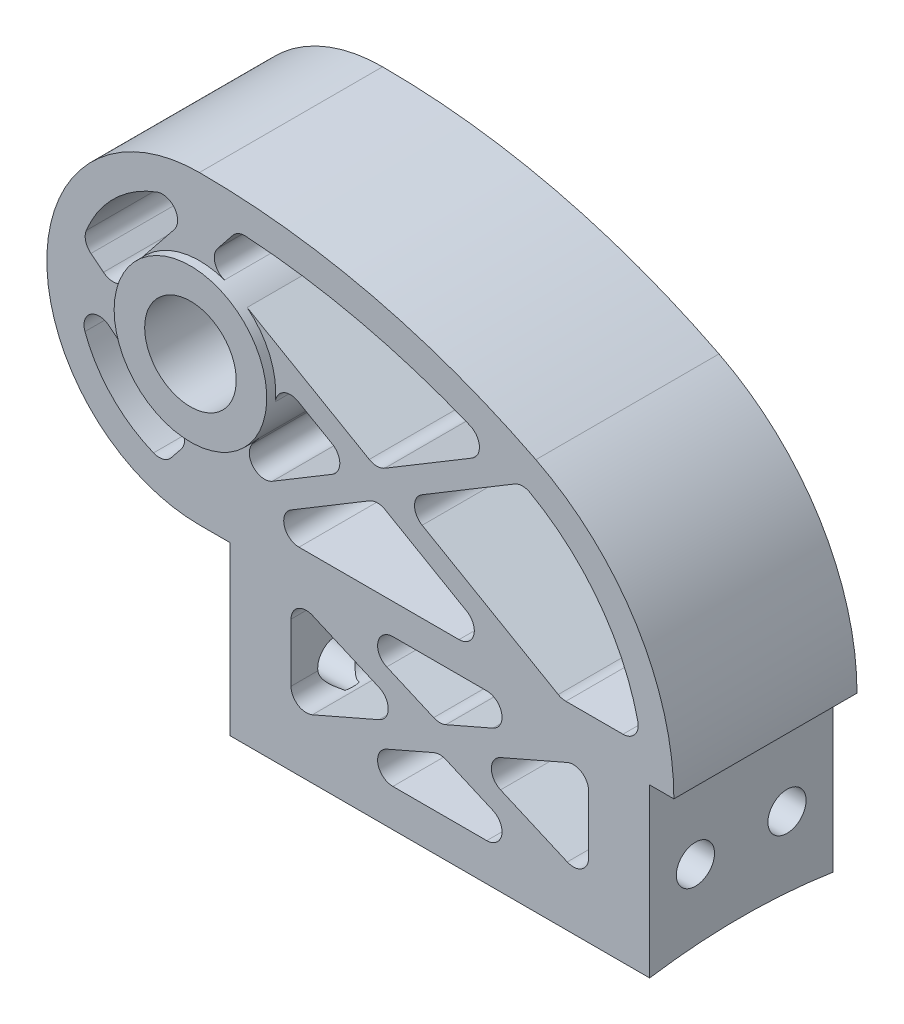
SolidWorks part; units mm, degrees
note: '?' marks a value the reader was unsure of.
material "7075-T6 (SN)"
ref_plane "Front Plane" through (0, 0, 0) normal (0, 0, 1) x (1, 0, 0)
ref_plane "Top Plane" through (0, 0, 0) normal (0, 1, 0) x (1, 0, 0)
ref_plane "Right Plane" through (0, 0, 0) normal (1, 0, 0) x (0, 0, -1)
sketch "frontal_shape" plane through (0, 0, 0) normal (0, 0, 1) x (1, 0, 0)
  line L0 (2, -10) -> (0, -10)
  line L1 (2, -10) -> (29.5, -10) construction
  line L2 (2, -10) -> (2, -20.5)
  line L3 (2, -20.5) -> (29.5, -20.5)
  line L4 (29.5, -10) -> (29.5, -20.5)
  line L5 (29.5, -10) -> (31.0875, -10)
  line L6 (31.0875, -10) -> (31.0875, -20.5) construction
  line L7 (31.0875, -20.5) -> (29.5, -20.5) construction
  line L8 (22.0449, 4.7276) -> (0, -8) construction
  line L9 (0, -10) -> (0, -8) construction
  circle A0 centre (0, 0) radius 3
  arc A1 (0, 10) -> (0, -10) centre (0, 0) ccw
  arc A2 (0, 10) -> (22.0449, 4.7276) centre (0, -38.7233) cw
  arc A3 (31.0875, -10) -> (22.0449, 4.7276) centre (14.5728, -10) ccw
  circle A4 centre (0, 0) radius 5
  point P7 (15.75, -10)
  point P16 (15.75, -20.5)
  dimension "shoulder_bold_diam" = 6
  dimension "abad_outer_diam" = 20
  dimension "spacer_diam" = 10
  dimension "plate_thickness" = 1.5875
  dimension "motor_thickness" = 27.5
  dimension "tab_height" = 10.5
  dimension "rotation_axis_to_motor_face" = 2
  dimension "wall_thickness" = 2
  dimension "support_angle" = 30
ref_plane "Plane1" through (2, 0, 0) normal (1, 0, 0) x (0, 0, -1)
sketch "sagittal_shape" plane through (2, 0, 0) normal (1, 0, 0) x (0, 0, -1)
  line L0 (0, -60) -> (0, -20.5) construction
  line L1 (0, -10) -> (0, -20.5) construction
  line L2 (0, 10) -> (0, 4.7276) construction
  line L4 (-6, -20.9584) -> (-6, 10)
  line L5 (-6, 10) -> (6, 10)
  line L6 (6, -20.9584) -> (6, 10)
  line L7 (6, 0) -> (6.59, 0) construction
  circle A0 centre (0, -60) radius 39.5 construction
  arc A1 (-6, -20.9584) -> (6, -20.9584) centre (0, -60) cw
  point P12 (0, 10)
  dimension "motor_diam" = 79
  dimension "thickness" = 12
  dimension "spacer_thickness" = 0.59
sketch "inner_structure" plane through (0, 0, 0) normal (0, 0, 1) x (1, 0, 0)
  line L2 (2, -10) -> (29.5, -10) construction
  line L5 (-3.9031, 3.125) -> (3.125, 3.9031) construction
  line L6 (3.125, 3.9031) -> (3.9031, -3.125) construction
  line L7 (-3.125, -3.9031) -> (-3.9031, 3.125) construction
  line L8 (3.9031, -3.125) -> (-3.125, -3.9031) construction
  line L10 (0, -8) -> (28.949, -8) construction
  line L11 (2, -18.5) -> (6, -18.5) construction
  line L12 (6, -10) -> (25.5, -10) construction
  line L13 (6, -10) -> (6, -18.5) construction
  line L14 (6, -18.5) -> (25.5, -18.5) construction
  line L15 (25.5, -10) -> (25.5, -18.5) construction
  line L16 (2, -10) -> (2, -20.5) construction
  line L17 (25.5, -18.5) -> (29.5, -18.5) construction
  line L18 (29.5, -10) -> (29.5, -20.5) construction
  line L19 (0, 8) -> (0, 10) construction
  line L20 (6, -18.5) -> (6, -20.5) construction
  line L21 (2, -20.5) -> (29.5, -20.5) construction
  line L22 (6, -10) -> (25.5, -18.5) construction
  line L23 (25.5, -10) -> (6, -18.5) construction
  line L24 (0, 8) -> (-3.9031, 3.125) construction
  line L25 (2.5081, 7.9326) -> (0.1581, 4.9975) construction
  line L26 (-8, 0) -> (-3.125, -3.9031) construction
  line L27 (-7.6643, 2.2932) -> (-4.9975, 0.1581) construction
  line L28 (-2.2932, -7.6643) -> (-0.1581, -4.9975) construction
  line L29 (3.9031, -3.125) -> (0, -8) construction
  line L30 (3.125, 3.9031) -> (23.7418, -8) construction
  line L31 (20.7418, -8) -> (4.8615, 1.1685) construction
  line L32 (0, -8) -> (19.4415, 3.6738) construction
  line L33 (2.9138, -8) -> (21.14, 2.944) construction
  line L34 (1.3331, 6.4651) -> (-0.2281, 7.7151) construction
  line L35 (-6.3309, 1.2257) -> (-7.5809, -0.3356) construction
  line L36 (-1.2257, -6.3309) -> (0.3356, -7.5809) construction
  line L37 (12.8017, -3.4158) -> (13.5517, -2.1167) construction
  line L38 (9.7207, -2.1631) -> (10.4929, -3.4491) construction
  line L39 (7.8769, -10) -> (15.75, -13.4318) construction
  line L40 (15.75, -13.4318) -> (23.6231, -10) construction
  line L41 (25.5, -10.8182) -> (17.6269, -14.25) construction
  line L42 (17.6269, -14.25) -> (25.5, -17.6818) construction
  line L43 (7.8769, -18.5) -> (15.75, -15.0682) construction
  line L44 (15.75, -15.0682) -> (23.6231, -18.5) construction
  line L46 (6, -10.8182) -> (13.8731, -14.25) construction
  line L47 (13.8731, -14.25) -> (6, -17.6818) construction
  line L48 (11.8135, -11.7159) -> (11.2141, -13.091) construction
  line L49 (9.9365, -15.9659) -> (10.5359, -17.341) construction
  arc A1 (0, 8) -> (0, -8) centre (0, 0) ccw construction
  circle A2 centre (0, 0) radius 5 construction
  arc A4 (29.0875, -10) -> (21.14, 2.944) centre (14.5728, -10) ccw
  arc A5 (21.14, 2.944) -> (0, 8) centre (0, -38.7233) ccw
  arc A6 (28.949, -8) -> (21.14, 2.944) centre (14.5728, -10) ccw construction
  arc A7 (21.14, 2.944) -> (0, 8) centre (0, -38.7233) ccw construction
  point P71 (10.2362, -16.6534)
  point P74 (11.5138, -12.4034)
  dimension "thread_thickness" = 4
  dimension "internal_thickness" = 1.5
  dimension "hub_thickness" = 2
  dimension "wall_thickness" = 2
  dimension "support_angle" = 30
sketch "Sketch4" plane through (0, 0, 0) normal (0, 0, 1) x (1, 0, 0)
  line L0 (2, -10) -> (2, -20.5) construction
  line L2 (29.5, -10) -> (29.5, -20.5) construction
  line L3 (29.5, -10) -> (31.0875, -10) construction
  line L4 (2, -10) -> (0, -10) construction
  line L5 (2, -10) -> (2, -20.9584)
  line L6 (2, -20.9584) -> (29.5, -20.9584)
  line L7 (29.5, -10) -> (29.5, -20.9584)
  line L8 (29.5, -10) -> (31.0875, -10)
  line L9 (2, -10) -> (0, -10)
  arc A0 (0, 10) -> (0, -10) centre (0, 0) ccw construction
  arc A1 (22.0449, 4.7276) -> (0, 10) centre (0, -38.7233) ccw construction
  arc A2 (0, 10) -> (0, -10) centre (0, 0) ccw
  arc A3 (22.0449, 4.7276) -> (0, 10) centre (0, -38.7233) ccw
  arc A4 (31.0875, -10) -> (22.0449, 4.7276) centre (14.5728, -10) ccw construction
  arc A5 (31.0875, -10) -> (22.0449, 4.7276) centre (14.5728, -10) ccw
  circle A6 centre (0, 0) radius 3 construction
  circle A7 centre (0, 0) radius 3
extrude "primary_shape" add sketch "Sketch4" against normal up to vertex (6 mm away) and the other way up to vertex (6 mm away) up to point (2, 10, -6) other way up to point (2, 10, 6)
sketch "Sketch5" plane through (0, 0, -6) normal (0, 0, -1) x (-1, 0, 0)
  circle A0 centre (0, 0) radius 3
  circle A1 centre (0, 0) radius 5
  circle A2 centre (0, 0) radius 3 construction
  circle A3 centre (0, 0) radius 5 construction
extrude "spacer" add sketch "Sketch5" along normal up to vertex (0.59 mm away) up to point (2, 0, -6.59)
mirror "spacer_mirror" about plane through (0, 0, 0) normal (0, 0, 1) of "spacer"
sketch "Sketch7" plane through (2, 0, 0) normal (-1, 0, 0) x (0, 0, 1)
  line L0 (-6, -20.9584) -> (6, -20.9584) construction
  line L1 (-6, -20.9584) -> (6, -20.9584)
  arc A0 (-6, -20.9584) -> (6, -20.9584) centre (0, -60) cw
extrude "motor_cuttout" cut sketch "Sketch7" against normal up to next
sketch "Sketch8" plane through (0, 0, 6) normal (0, 0, 1) x (1, 0, 0)
  line L0 (7.8769, -10) -> (15.75, -13.4318)
  line L1 (15.75, -13.4318) -> (23.6231, -10)
  line L2 (23.6231, -10) -> (7.8769, -10)
  line L3 (6, -10.8182) -> (13.8731, -14.25)
  line L4 (13.8731, -14.25) -> (6, -17.6818)
  line L5 (6, -17.6818) -> (6, -10.8182)
  line L6 (7.8769, -18.5) -> (15.75, -15.0682)
  line L7 (15.75, -15.0682) -> (23.6231, -18.5)
  line L8 (23.6231, -18.5) -> (7.8769, -18.5)
  line L9 (25.5, -10.8182) -> (25.5, -17.6818)
  line L10 (25.5, -17.6818) -> (17.6269, -14.25)
  line L11 (17.6269, -14.25) -> (25.5, -10.8182)
  line L12 (2.9138, -8) -> (11.6529, -2.7525)
  line L13 (20.7418, -8) -> (4.8615, 1.1685) construction
  line L14 (2.9138, -8) -> (21.14, 2.944) construction
  line L15 (11.6529, -2.7525) -> (20.7418, -8)
  line L16 (20.7418, -8) -> (2.9138, -8)
  line L17 (21.14, 2.944) -> (13.1235, -1.8695)
  line L18 (3.125, 3.9031) -> (23.7418, -8) construction
  line L19 (13.1235, -1.8695) -> (23.7418, -8)
  line L20 (23.7418, -8) -> (28.949, -8)
  line L21 (19.5258, 3.7244) -> (11.638, -1.0119)
  line L22 (0, -8) -> (19.4415, 3.6738) construction
  line L23 (11.638, -1.0119) -> (3.125, 3.9031)
  line L24 (0.1581, 4.9975) -> (2.5081, 7.9326)
  line L25 (4.8615, 1.1685) -> (10.1674, -1.8949)
  line L26 (10.1674, -1.8949) -> (0, -8)
  line L27 (0, -8) -> (3.9031, -3.125)
  line L28 (-0.1581, -4.9975) -> (-2.2932, -7.6643)
  line L29 (-8, 0) -> (-3.125, -3.9031)
  line L30 (-7.6643, 2.2932) -> (-4.9975, 0.1581)
  line L31 (0, 8) -> (-3.9031, 3.125)
  circle A0 centre (0, 0) radius 5 construction
  arc A1 (0, 8) -> (0, -8) centre (0, 0) ccw construction
  arc A3 (21.14, 2.944) -> (0, 8) centre (0, -38.7233) ccw construction
  arc A4 (0, 8) -> (-7.6643, 2.2932) centre (0, 0) ccw
  arc A7 (-3.125, -3.9031) -> (-0.1581, -4.9975) centre (0, 0) ccw
  arc A8 (-8, 0) -> (-2.2932, -7.6643) centre (0, 0) ccw
  arc A9 (-3.9031, 3.125) -> (-4.9975, 0.1581) centre (0, 0) ccw
  arc A10 (3.125, 3.9031) -> (0.1581, 4.9975) centre (0, 0) ccw
  arc A11 (3.9031, -3.125) -> (4.8615, 1.1685) centre (0, 0) ccw
  arc A13 (28.949, -8) -> (21.14, 2.944) centre (14.5728, -10) ccw
  arc A14 (19.5258, 3.7244) -> (2.5081, 7.9326) centre (0, -38.7233) ccw
  arc A15 (28.949, -8) -> (21.14, 2.944) centre (14.5728, -10) ccw construction
extrude "inner_cuttout" cut sketch "Sketch8" against normal up to next
fillet "Fillet1" radius 1 32 edges at (6, -17.6818, 0) (23.6231, -18.5, 0) (7.8769, -18.5, 0) (13.8731, -14.25, 0) (15.75, -15.0682, 0) (17.6269, -14.25, 0) (25.5, -17.6818, 0) (25.5, -10.8182, 0) (23.6231, -10, 0) (15.75, -13.4318, 0) (7.8769, -10, 0) (6, -10.8182, 0) (2.9138, -8, 0) (20.7418, -8, 0) (23.7418, -8, 0) (0.1581, 4.9975, 0) (11.638, -1.0119, 0) (13.1235, -1.8695, 0) (11.6529, -2.7525, 0) (10.1674, -1.8949, 0) (4.8615, 1.1685, 0) (0, -8, 0) (-0.1581, -4.9975, 0) (-2.2932, -7.6643, 0) (-8, 0, 0) (-4.9975, 0.1581, 0) (-7.6643, 2.2932, 0) (0, 8, 0) (2.5081, 7.9326, 0) (28.949, -8, 0) (19.5258, 3.7244, 0) (21.14, 2.944, 0)
ref_plane "Plane2" through (15.75, -20.9584, -6) normal (1, 0, 0) x (0, 0, -1)
hole_wizard "Tap Drill for M3x0.5 Tap1" positions "Sketch9" profile "Sketch10" hole size "M3x0.5" standard "BSI"
sketch "Sketch9" plane through (29.5, 0, 0) normal (1, 0, 0) x (0, 0, -1)
  line L0 (-3, -16) -> (3, -16) construction
  line L3 (0, -16) -> (0, -10) construction
  line L4 (6, -10) -> (-6, -10) construction
  point P0 (-3, -16)
  point P2 (3, -16)
  dimension "D1" = 6
  dimension "mounting_hole_dist_from_shoulder" = 6
sketch "Sketch10" plane through (29.5, -16, 3) normal (0, 1, 0) x (0, 0, -1)
  line L0 (0, 0) -> (0, 5.7511)
  line L1 (0, 5.7511) -> (1.25, 5)
  line L2 (1.25, 5) -> (1.25, 0)
  line L5 (1.25, 0) -> (0, 0)
  line L10 (0, 5.7511) -> (-1.25, 5) construction
  line L11 (0, -6.35) -> (0, 107.95) construction
  dimension "Hole Dia." = 2.5
  dimension "Hole Depth" = 5
  dimension "Drill Angle" = 118
mirror "Mirror2" about plane through (15.75, -20.9584, -6) normal (1, 0, 0) of "Tap Drill for M3x0.5 Tap1"
ref_axis "Axis1" through (29.5, -60, 0) along (-1, 0, 0)?
ref_plane "Plane3" [suppressed] through (6, 0, 0) normal (-1, 0, 0) x (0, 0, 1)
sketch "Sketch11" [suppressed] plane through (6, 0, 0) normal (-1, 0, 0) x (0, 0, 1)
  line L7 (4.5877, -13.25) -> (1.4123, -13.25)
  line L8 (1.4123, -13.25) -> (-0.1754, -16)
  line L9 (-0.1754, -16) -> (1.4123, -18.75)
  line L10 (1.4123, -18.75) -> (4.5877, -18.75)
  line L11 (4.5877, -18.75) -> (6.1754, -16) construction
  line L12 (6.1754, -16) -> (4.5877, -13.25) construction
  line L16 (4.5877, -13.25) -> (6, -13.25)
  line L17 (6, -10) -> (6, -22.4767) construction
  line L18 (6, -13.25) -> (6, -18.75)
  line L19 (6, -18.75) -> (4.5877, -18.75)
  circle A1 centre (3, -16) radius 2.75 construction
  dimension "D1" = 5.5
extrude "Cut-Extrude1" [suppressed] cut sketch "Sketch11" against normal blind 4
mirror "Mirror3" [suppressed] about plane through (0, 0, 0) normal (0, 0, 1)
ref_plane "Plane4" [suppressed] through (14.25, 0, 0) normal (1, 0, 0) x (0, 0, -1)
mirror "Mirror4" [suppressed] about plane through (14.25, 0, 0) normal (1, 0, 0)
hole_wizard "M3 Clearance Hole1" [suppressed] positions "Sketch12" profile "Sketch13" hole size "M3" standard "BSI"
sketch "Sketch12" plane through (26.5, 0, 0) normal (1, 0, 0) x (0, 0, -1)
  point P0 (-3, -16)
  point P3 (3, -16)
sketch "Sketch13" plane through (26.5, -16, 3) normal (0, 1, 0) x (0, 0, -1)
  line L0 (0, 0) -> (0, 36.5)
  line L1 (0, 36.5) -> (1.8, 36.5)
  line L2 (1.8, 36.5) -> (1.8, 0)
  line L5 (1.8, 0) -> (0, 0)
  line L11 (0, -6.35) -> (0, 107.95) construction
  dimension "Thru Hole Dia." = 3.6
  dimension "Thru Hole Depth" = 36.5
ref_axis "Axis2" through (24.5, -16, 3) along (1, 0, 0)?
ref_axis "Axis3" through (24.5, -16, -3) along (1, 0, 0)?
ref_axis "Axis4" through (7, -16, -3) along (-1, 0, 0)?
ref_axis "Axis5" through (7, -16, 3) along (-1, 0, 0)?
